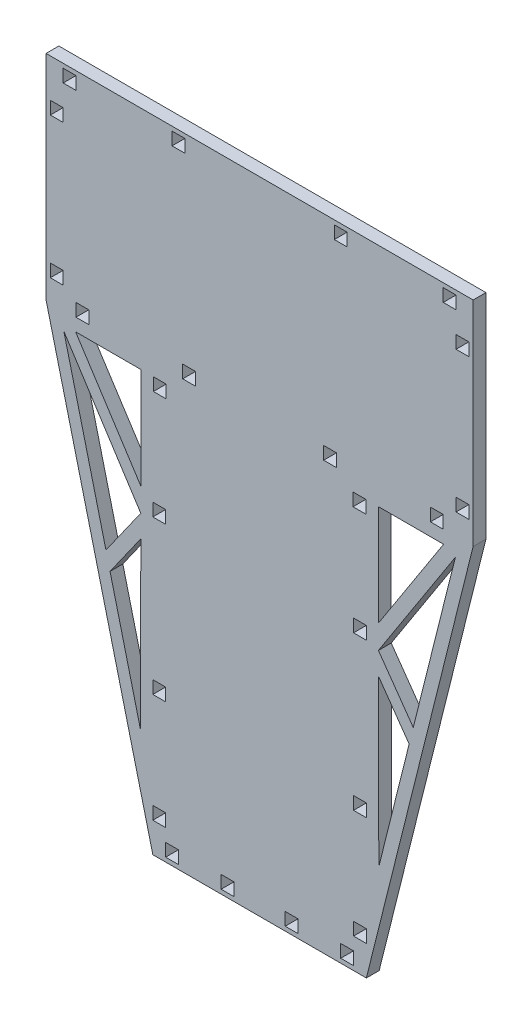
SolidWorks part; units mm, degrees
material "Pine"
ref_plane "정면" through (0, 0, 0) normal (0, 0, 1) x (1, 0, 0)
ref_plane "윗면" through (0, 0, 0) normal (0, 1, 0) x (1, 0, 0)
ref_plane "우측면" through (0, 0, 0) normal (1, 0, 0) x (0, 0, -1)
sketch "Sketch1" plane through (0, 0, 0) normal (0, 0, 1) x (1, 0, 0)
  line L0 (0, -33.3878) -> (0, 330.1576) construction
  line L5 (100, 300) -> (100, 200)
  line L6 (100, 200) -> (50, 0)
  line L7 (50, 0) -> (-50, 0)
  line L8 (-100, 300) -> (100, 300)
  line L9 (-100, 200) -> (-50, 0)
  line L10 (-100, 300) -> (-100, 200)
  line L11 (130.6916, 200) -> (43.0423, 200) construction
  point P9 (0, 300)
  point P10 (0, 0)
  point P11 (0, 300)
  point P12 (0, 0)
  dimension "D1" = 100
  dimension "D2" = 100
  dimension "D3" = 50
  dimension "D4" = 300
extrude "Boss-Extrude1" add sketch "Sketch1" along normal blind 6
sketch "Sketch4" plane through (0, 0, 0) normal (0, 0, -1) x (-1, 0, 0)
  line L0 (-252.2182, 250.3111) -> (-252.2182, 244.3111)
  line L1 (-252.2182, 244.3111) -> (-246.2182, 244.3111)
  line L2 (-246.2182, 244.3111) -> (-246.2182, 250.3111)
  line L3 (-246.2182, 250.3111) -> (-252.2182, 250.3111)
  line L4 (0, -23.7319) -> (0, 420.3937) construction
  line L5 (-98, 282) -> (-98, 276)
  line L6 (-98, 276) -> (-92, 276)
  line L7 (-92, 276) -> (-92, 282)
  line L8 (-92, 282) -> (-98, 282)
  line L13 (-98, 216) -> (-98, 210)
  line L14 (-98, 210) -> (-92, 210)
  line L15 (-92, 210) -> (-92, 216)
  line L16 (-92, 216) -> (-98, 216)
  line L17 (-92, 298) -> (-92, 292)
  line L18 (-92, 292) -> (-86, 292)
  line L19 (-86, 292) -> (-86, 298)
  line L20 (-86, 298) -> (-92, 298)
  line L21 (-44, 8) -> (-44, 2)
  line L22 (-44, 2) -> (-38, 2)
  line L23 (-38, 2) -> (-38, 8)
  line L24 (-38, 8) -> (-44, 8)
  line L25 (-100, 200) -> (-100, 300) construction
  line L26 (-100, 300) -> (100, 300) construction
  line L27 (-41, 298) -> (-41, 292)
  line L28 (-41, 292) -> (-35, 292)
  line L29 (-35, 292) -> (-35, 298)
  line L30 (-35, 298) -> (-41, 298)
  line L31 (-100, 200) -> (100, 200) construction
  line L34 (-86, 206) -> (-86, 200)
  line L35 (-86, 200) -> (-80, 200)
  line L36 (-80, 200) -> (-80, 206)
  line L37 (-80, 206) -> (-86, 206)
  line L38 (-66.3861, 200) -> (33.6139, 200) construction
  line L39 (-36, 206) -> (-36, 200)
  line L40 (-36, 200) -> (-30, 200)
  line L41 (-30, 200) -> (-30, 206)
  line L42 (-30, 206) -> (-36, 206)
  line L43 (50, 0) -> (-50, 0) construction
  line L44 (-18, 8) -> (-18, 2)
  line L45 (-18, 2) -> (-12, 2)
  line L46 (-12, 2) -> (-12, 8)
  line L47 (-12, 8) -> (-18, 8)
  line L56 (-115.4914, 40.7643) -> (120.5995, 40.7643) construction
  line L57 (-36, 26.0413) -> (-36, 163.8526) construction
  line L58 (-50, 20) -> (-44, 20)
  line L59 (-50, 14) -> (-50, 20)
  line L60 (-44, 14) -> (-50, 14)
  line L61 (-44, 20) -> (-44, 14)
  line L62 (-50, 0) -> (-50, 67.852) construction
  line L63 (-50, 71) -> (-44, 71)
  line L64 (-50, 65) -> (-50, 71)
  line L65 (-44, 65) -> (-50, 65)
  line L66 (-44, 71) -> (-44, 65)
  line L67 (-50, 19.2159) -> (-50, 220.6335) construction
  line L68 (-49.7488, 194) -> (-43.7488, 194)
  line L69 (-49.7488, 188) -> (-49.7488, 194)
  line L70 (-43.7488, 188) -> (-49.7488, 188)
  line L71 (-43.7488, 194) -> (-43.7488, 188)
  line L72 (-49.7488, 174) -> (-49.7488, 241.852) construction
  line L73 (-50, 143) -> (-44, 143)
  line L74 (-50, 137) -> (-50, 143)
  line L75 (-44, 137) -> (-50, 137)
  line L76 (-44, 143) -> (-44, 137)
  line L77 (-50, 142.4727) -> (-50, 210.3247) construction
  line L78 (35, 298) -> (41, 298)
  line L79 (35, 292) -> (35, 298)
  line L80 (41, 292) -> (35, 292)
  line L81 (41, 298) -> (41, 292)
  line L82 (86, 298) -> (92, 298)
  line L83 (86, 292) -> (86, 298)
  line L84 (92, 292) -> (86, 292)
  line L85 (92, 298) -> (92, 292)
  line L86 (92, 282) -> (98, 282)
  line L87 (92, 276) -> (92, 282)
  line L88 (98, 276) -> (92, 276)
  line L89 (98, 282) -> (98, 276)
  line L90 (80, 206) -> (86, 206)
  line L91 (80, 200) -> (80, 206)
  line L92 (86, 200) -> (80, 200)
  line L93 (86, 206) -> (86, 200)
  line L94 (92, 216) -> (98, 216)
  line L95 (92, 210) -> (92, 216)
  line L96 (98, 210) -> (92, 210)
  line L97 (98, 216) -> (98, 210)
  line L98 (49.7488, 174) -> (49.7488, 241.852) construction
  line L99 (43.7488, 194) -> (43.7488, 188)
  line L100 (43.7488, 188) -> (49.7488, 188)
  line L101 (49.7488, 188) -> (49.7488, 194)
  line L102 (49.7488, 194) -> (43.7488, 194)
  line L103 (44, 143) -> (44, 137)
  line L104 (44, 137) -> (50, 137)
  line L105 (50, 137) -> (50, 143)
  line L106 (50, 143) -> (44, 143)
  line L107 (44, 71) -> (44, 65)
  line L108 (44, 65) -> (50, 65)
  line L109 (50, 65) -> (50, 71)
  line L110 (50, 71) -> (44, 71)
  line L111 (44, 20) -> (44, 14)
  line L112 (44, 14) -> (50, 14)
  line L113 (50, 14) -> (50, 20)
  line L114 (50, 20) -> (44, 20)
  line L115 (38, 8) -> (44, 8)
  line L116 (38, 2) -> (38, 8)
  line L117 (44, 2) -> (38, 2)
  line L118 (44, 8) -> (44, 2)
  line L119 (12, 8) -> (18, 8)
  line L120 (12, 2) -> (12, 8)
  line L121 (18, 2) -> (12, 2)
  line L122 (18, 8) -> (18, 2)
  line L123 (66.3861, 200) -> (-33.6139, 200) construction
  line L124 (30, 206) -> (36, 206)
  line L125 (30, 200) -> (30, 206)
  line L126 (36, 200) -> (30, 200)
  line L127 (36, 206) -> (36, 200)
  line L128 (55.6221, 194) -> (86.1713, 194)
  line L129 (86.1713, 194) -> (55.6221, 146.7107)
  line L130 (55.6221, 146.7107) -> (55.6221, 194)
  line L131 (55.6401, 135.6812) -> (91.6847, 191.4772)
  line L140 (91.6847, 191.4772) -> (54.3218, 42.026) construction
  line L141 (91.6847, 191.4772) -> (71.9623, 112.588)
  line L142 (100, 200) -> (50, 0) construction
  line L143 (71.9623, 112.588) -> (55.6401, 135.6812)
  line L144 (55.6221, 197.4602) -> (55.6221, 31.1826) construction
  line L145 (70.0425, 104.9088) -> (55.6221, 125.3113)
  line L146 (55.6221, 125.3113) -> (55.8322, 48.0673)
  line L147 (55.8322, 48.0673) -> (70.0425, 104.9088)
  line L148 (-55.8322, 48.0673) -> (-70.0425, 104.9088)
  line L149 (-55.6221, 125.3113) -> (-55.8322, 48.0673)
  line L150 (-70.0425, 104.9088) -> (-55.6221, 125.3113)
  line L151 (-71.9623, 112.588) -> (-55.6401, 135.6812)
  line L152 (-91.6847, 191.4772) -> (-71.9623, 112.588)
  line L153 (-55.6401, 135.6812) -> (-91.6847, 191.4772)
  line L154 (-86.1713, 194) -> (-55.6221, 146.7107)
  line L155 (-55.6221, 146.7107) -> (-55.6221, 194)
  line L156 (-55.6221, 194) -> (-86.1713, 194)
  point P27 (-92, 295)
  point P32 (-41, 295)
  point P33 (-95, 282)
  point P34 (-98, 213)
  point P98 (0, 200)
  point P153 (70.0425, 104.9088)
  dimension "D1" = 6
  dimension "D2" = 6
  dimension "D3" = 2
  dimension "D4" = 2
  dimension "D5" = 8
  dimension "D6" = 6
  dimension "D7" = 2
  dimension "D8" = 45
  dimension "D9" = 6
  dimension "D10" = 6
  dimension "D11" = 6
  dimension "D12" = 10
  dimension "D13" = 10
  dimension "D14" = 2
  dimension "D15" = 6
  dimension "D16" = 6
  dimension "D17" = 6
  dimension "D18" = 6
  dimension "D19" = 6
  dimension "D20" = 6
  dimension "D21" = 14
  dimension "D22" = 6
  dimension "D23" = 6
  dimension "D24" = 44
  dimension "D25" = 2
  dimension "D26" = 6
  dimension "D27" = 6
  dimension "D28" = 6
  dimension "D29" = 6
  dimension "D30" = 6
  dimension "D31" = 20
  dimension "D32" = 90
  dimension "D33" = 6
  dimension "D34" = 6
  dimension "D35" = 14
  dimension "D36" = 6
  dimension "D37" = 6
  dimension "D38" = 45
  dimension "D39" = 6
  dimension "D40" = 6
  dimension "D41" = 6
  dimension "D42" = 6
  dimension "D43" = 6
  dimension "D44" = 45
  dimension "D45" = 6
  dimension "D46" = 6
  dimension "D47" = 6
extrude "Cut-Extrude2" cut sketch "Sketch4" against normal blind 6
